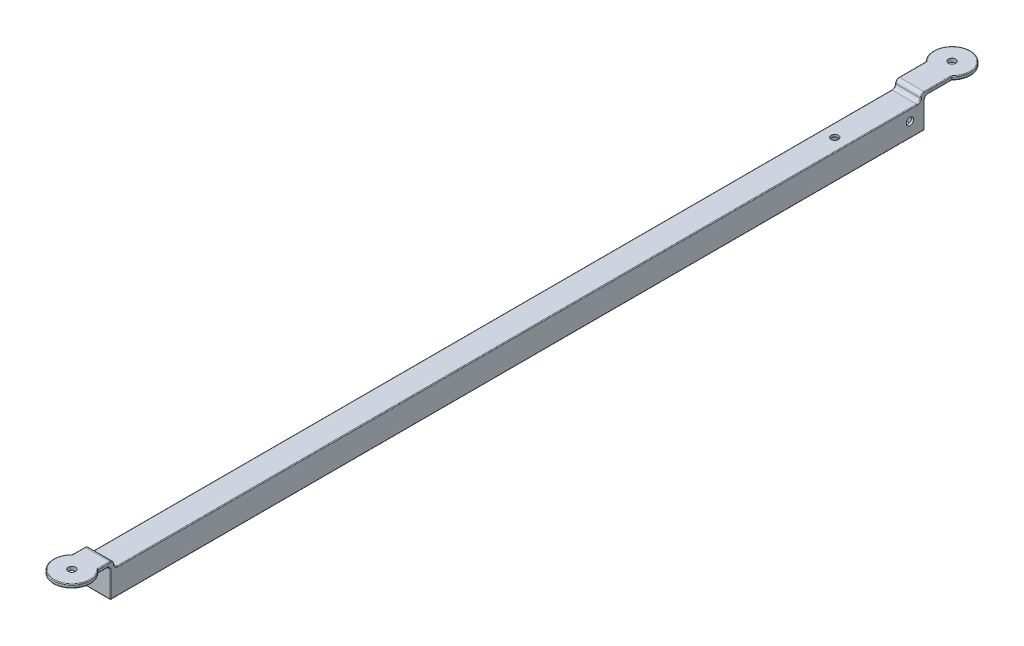
SolidWorks part; units mm, degrees
ref_plane "前视基准面" through (0, 0, 0) normal (0, 0, 1) x (1, 0, 0)
ref_plane "上视基准面" through (0, 0, 0) normal (0, 1, 0) x (1, 0, 0)
ref_plane "右视基准面" through (0, 0, 0) normal (1, 0, 0) x (0, 0, -1)
other "Configuration Table"
sketch "草图1" plane through (0, 0, 0) normal (0, 0, 1) x (1, 0, 0)
  line L1 (-17.5, 17.5) -> (17.5, 17.5)
  line L2 (-17.5, 17.5) -> (-17.5, -17.5)
  line L3 (-17.5, -17.5) -> (17.5, -17.5)
  line L4 (17.5, 17.5) -> (17.5, -17.5)
  line L5 (-17.5, 17.5) -> (17.5, -17.5) construction
  line L6 (-17.5, -17.5) -> (17.5, 17.5) construction
  point P0 (0, 0)
  dimension "D1" = 35
extrude "拉伸-薄壁1" add sketch "草图1" along normal blind 1100 thin thin type one direction reverse wall 3
sketch "草图2" plane through (0, 0, 1100) normal (0, 0, 1) x (1, 0, 0)
  line L0 (-17.5, -17.5) -> (17.5, -17.5) construction
  line L1 (17.5, -17.5) -> (-17.5, -17.5)
  line L2 (17.5, -17.5) -> (17.5, 27.5)
  line L3 (17.5, 27.5) -> (-17.5, 27.5)
  line L4 (-17.5, -17.5) -> (-17.5, 27.5)
  line L5 (17.5, -17.5) -> (-17.5, 27.5) construction
  line L6 (17.5, 27.5) -> (-17.5, -17.5) construction
  line L7 (-17.5, 17.5) -> (-17.5, -17.5) construction
  point P4 (0, 5)
  dimension "D1" = 45
extrude "凸台-拉伸1" add sketch "草图2" along normal blind 5
sketch "草图6" plane through (0, 27.5, 0) normal (0, 1, 0) x (1, 0, 0)
  line L0 (-17.5, -1100) -> (-17.5, 0) construction
  line L1 (-17.5, -1100) -> (17.5, -1100)
  line L2 (-17.5, -1100) -> (-17.5, -1140)
  line L3 (-17.5, -1140) -> (17.5, -1140)
  line L4 (17.5, -1100) -> (17.5, -1140)
  line L5 (-17.5, -1100) -> (17.5, -1140) construction
  line L6 (-17.5, -1140) -> (17.5, -1100) construction
  line L7 (17.5, -1100) -> (-17.5, -1100) construction
  circle A0 centre (0, -1140) radius 5
  circle A1 centre (0, -1140) radius 25
  point P4 (0, -1120)
  line M7 (-17.5, -1105) -> (17.5, -1105)
  dimension "D2" = 10
  dimension "D3" = 50
  dimension "D1" = 40
extrude "凸台-拉伸2" add sketch "草图6" against normal blind 5 contours A1 L4 L2 M7 | L2 A1 L4 L3 A0 | L4 A1 L2 L3 A0 region at (0, 27.5, 1111.2892) region at (0, 27.5, 1128.034) region at (0, 27.5, 1148.0447)
sketch "草图5" plane through (0, 17.5, 0) normal (0, 1, 0) x (1, 0, 0)
  line L0 (0, 0) -> (0, -285.8834) construction
  line L1 (17.5, 0) -> (-17.5, 0) construction
  circle A0 centre (0, -100) radius 5
  dimension "D1" = 10
  dimension "D2" = 100
extrude "切除-拉伸1" cut sketch "草图5" against normal through all
sketch "草图7" plane through (0, 0, 0) normal (0, 0, -1) x (-1, 0, 0)
  line L0 (-17.5, -17.5) -> (-17.5, 17.5) construction
  line L1 (-17.5, -17.5) -> (17.5, -17.5)
  line L2 (-17.5, -17.5) -> (-17.5, 27.5)
  line L3 (-17.5, 27.5) -> (17.5, 27.5)
  line L4 (17.5, -17.5) -> (17.5, 27.5)
  line L5 (-17.5, -17.5) -> (17.5, 27.5) construction
  line L6 (-17.5, 27.5) -> (17.5, -17.5) construction
  point P4 (0, 5)
  dimension "D1" = 45
extrude "凸台-拉伸3" add sketch "草图7" along normal blind 5
sketch "草图8" plane through (0, 27.5, 0) normal (0, 1, 0) x (1, 0, 0)
  line L0 (-17.5, 0) -> (17.5, 0) construction
  line L1 (17.5, 0) -> (-17.5, 0)
  line L2 (17.5, 0) -> (17.5, 60)
  line L3 (17.5, 60) -> (-17.5, 60)
  line L4 (-17.5, 0) -> (-17.5, 60)
  line L5 (17.5, 0) -> (-17.5, 60) construction
  line L6 (17.5, 60) -> (-17.5, 0) construction
  line L7 (17.5, 5) -> (17.5, 0) construction
  circle A0 centre (0, 60) radius 5
  circle A1 centre (0, 60) radius 25
  point P4 (0, 30)
  line M9 (17.5, 5) -> (-17.5, 5)
  dimension "D2" = 10
  dimension "D3" = 50
  dimension "D1" = 60
extrude "凸台-拉伸4" add sketch "草图8" against normal blind 5 contours A1 L4 L2 M9 | L4 A1 L2 L3 A0 | L2 A1 L4 L3 A0 region at (0, 27.5, -21.1801) region at (0, 27.5, -48.034) region at (0, 27.5, -68.0447)
fillet "圆角1" radius 5 6 edges at (0, 17.5, 0) (0, 22.5, -5) (0, 27.5, 0) (0, 17.5, 1100) (0, 22.5, 1105) (0, 27.5, 1100)
fillet "圆角2" radius 1 39 edges at (0, 27.5, 1165) (0, 22.5, 1165) (0, 22.5, -85) (0, 27.5, -85) (17.5, 25, -42.1464) (17.5, 22.5, -26.0732) (17.5, 21.0355, -6.4645) (17.5, 0, -5) (17.5, -17.5, 550) (17.5, 0, 1105) (17.5, 21.0355, 1106.4645) (17.5, 22.5, 1116.0732) (17.5, 25, 1122.1464) (17.5, 27.5, 1113.5732) (17.5, 26.0355, 1101.4645) (17.5, 18.9645, 1098.5355) (17.5, 17.5, 550) (17.5, 18.9645, 1.4645) (17.5, 26.0355, -1.4645) (17.5, 27.5, -23.5732) (-17.5, 18.9645, 1.4645) (-17.5, 17.5, 550) (-17.5, 18.9645, 1098.5355) (-17.5, 26.0355, 1101.4645) (-17.5, 27.5, 1113.5732) (-17.5, 25, 1122.1464) (-17.5, 22.5, 1116.0732) (-17.5, 21.0355, 1106.4645) (-17.5, 0, 1105) (-17.5, -17.5, 550) (-17.5, 0, -5) (-17.5, 21.0355, -6.4645) (-17.5, 22.5, -26.0732) (-17.5, 25, -42.1464) (-17.5, 27.5, -23.5732) (-17.5, 26.0355, -1.4645) (0, -17.5, 1105) (0, -17.5, -5) (0, -17.5, 105)
sketch "草图9" plane through (17.5, 0, 0) normal (1, 0, 0) x (0, 0, -1)
  line L0 (5, 17.5) -> (5, -16.5) construction
  line L1 (5, 2.5) -> (-15, 2.5) construction
  line L2 (4, -17.5) -> (-1104, -17.5) construction
  circle A0 centre (-15, 2.5) radius 5
  dimension "D1" = 10
  dimension "D2" = 20
  dimension "D3" = 20
extrude "切除-拉伸2" cut sketch "草图9" against normal through all
